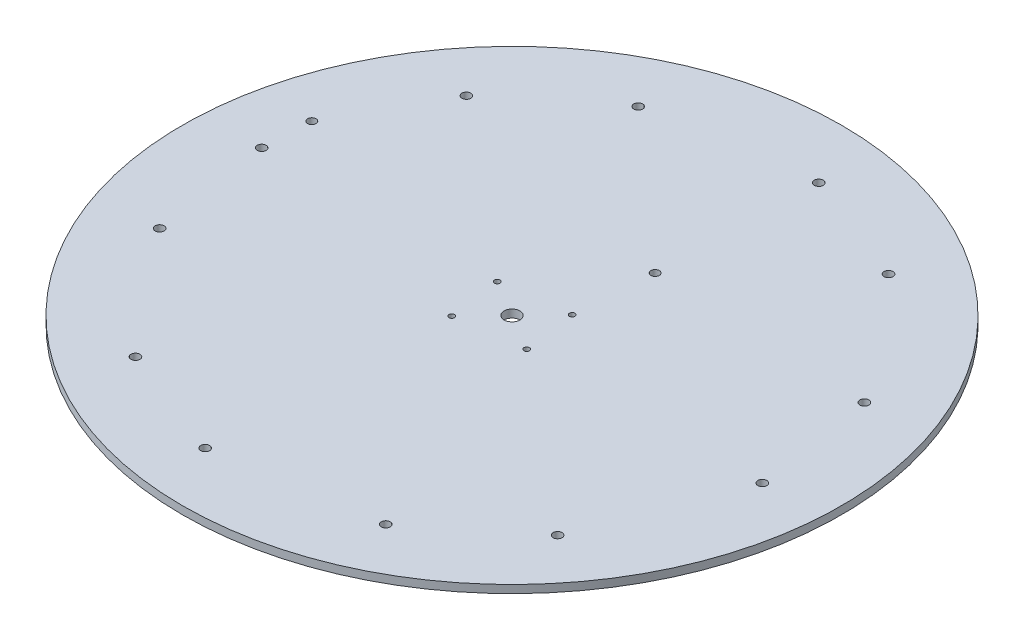
SolidWorks part; units mm, degrees
ref_plane "Front Plane" through (0, 0, 0) normal (0, 0, 1) x (1, 0, 0)
ref_plane "Top Plane" through (0, 0, 0) normal (0, 1, 0) x (1, 0, 0)
ref_plane "Right Plane" through (0, 0, 0) normal (1, 0, 0) x (0, 0, -1)
sketch "Sketch2" plane through (0, 0, 0) normal (0, 1, 0) x (1, 0, 0)
  circle A0 centre (0, 0) radius 125
  dimension "D1" = 250
extrude "Boss-Extrude1" add sketch "Sketch2" along normal blind 3
sketch "Sketch3" plane through (0, 3, 0) normal (0, 1, 0) x (1, 0, 0)
  line L4 (74.6446, 100.2656) -> (65.4599, 76.5843) construction
  line L5 (0, 0) -> (43.5629, 112.3204) construction
  line L6 (74.6446, 100.2656) -> (12.4813, 124.3753) construction
  line L7 (12.4813, 124.3753) -> (3.2966, 100.6941) construction
  line L8 (65.4599, 76.5843) -> (3.2966, 100.6941) construction
  circle A0 centre (0, 0) radius 125 construction
  circle A7 centre (57.8244, 84.9944) radius 1.7
  circle A8 centre (14.6061, 101.7564) radius 1.7
  circle A9 centre (44.6952, -92.5746) radius 1.7
  circle A10 centre (80.8206, -63.5274) radius 1.7
  circle A11 centre (-102.5195, 7.5802) radius 1.7
  circle A12 centre (-95.4267, -38.229) radius 1.7
  point P22 (0, 0)
  point P23 (0.4661, 0.2121)
  dimension "D2" = 3.4
  dimension "D1" = 25.4
  dimension "D3" = 5.08
  dimension "D5" = 66.675
  dimension "D6" = 3
  dimension "D4" = 10.16
extrude "Cut-Extrude1" cut sketch "Sketch3" against normal blind 26 and the other way blind 62
sketch "Sketch4" plane through (0, 3, 0) normal (0, 1, 0) x (1, 0, 0)
  circle A0 centre (0, 0) radius 3
  dimension "D1" = 6
extrude "Cut-Extrude2" cut sketch "Sketch4" against normal blind 33 and the other way blind 55
sketch "Sketch5" plane through (0, 0, 0) normal (0, -1, 0) x (1, 0, 0)
  circle A0 centre (-101.7781, -25.8548) radius 1.6
  circle A1 centre (13.2168, -41.0922) radius 1.6
  dimension "D1" = 3.2
  dimension "D2" = 3.2
extrude "Cut-Extrude3" cut sketch "Sketch5" against normal through all
sketch "Sketch6" plane through (0, 3, 0) normal (0, 1, 0) x (1, 0, 0)
  circle A0 centre (11.1984, 11.6251) radius 1.05
  circle A1 centre (13.8892, -8.3009) radius 1.05
  circle A2 centre (-11.1984, -11.6251) radius 1.05
  circle A3 centre (-13.8892, 8.3009) radius 1.05
extrude "Cut-Extrude4" cut sketch "Sketch6" against normal up to next
pattern_circular "CirPattern1" count 6 over 360 about axis through (0, 3, 0) along (0, 1, 0) of "Cut-Extrude1"
